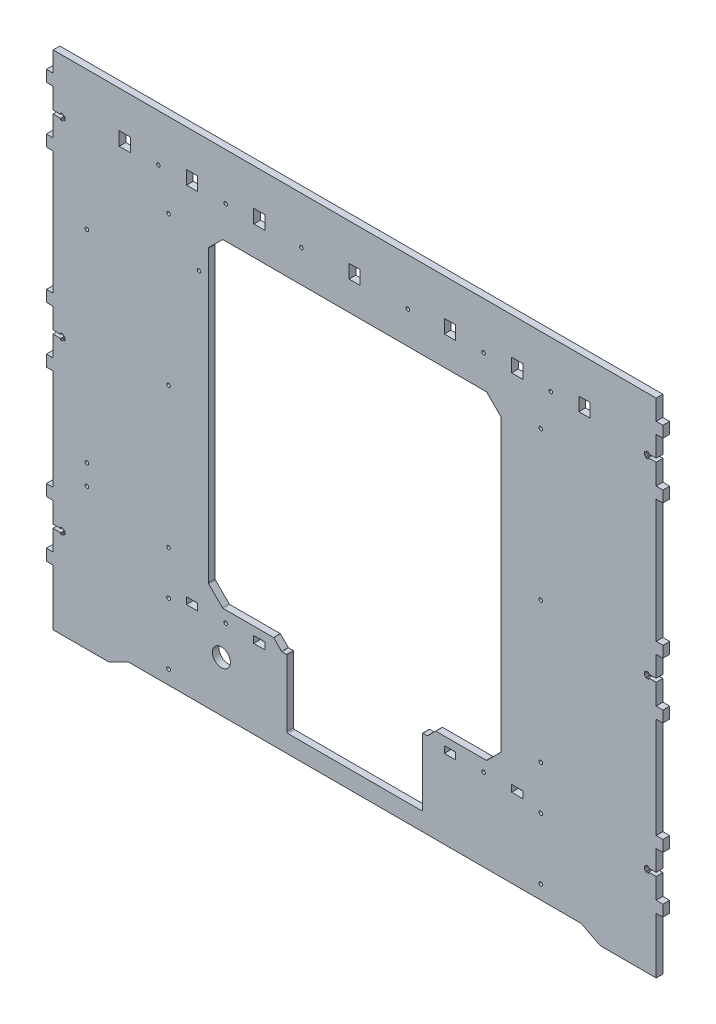
SolidWorks part; units mm, degrees
material "Клен"
ref_plane "Front" through (0, 0, 0) normal (0, 0, 1) x (1, 0, 0)
ref_plane "Top" through (0, 0, 0) normal (0, 1, 0) x (1, 0, 0)
ref_plane "Right" through (0, 0, 0) normal (1, 0, 0) x (0, 0, -1)
sketch "Эскиз2" plane through (0, 0, 0) normal (0, 0, 1) x (1, 0, 0)
  line L0 (400.4244, 482.0072) -> (-19.6784, 482.0072) construction
  line L1 (308.1919, 504.8221) -> (308.1919, 0) construction
  line L2 (39.1919, 504.8221) -> (39.1919, 18.7975) construction
  line L3 (33.1919, 504.8221) -> (33.1919, 18.7975) construction
  line L4 (228.1919, 149.8356) -> (228.1919, 102.1072) construction
  line L5 (168.1919, 135.3857) -> (168.1919, 108.8729) construction
  line L6 (193.1919, 141.9072) -> (193.1919, 108.8729) construction
  line L7 (260.6919, 457.1072) -> (260.6919, 439.2572) construction
  line L8 (228.1919, 461.9072) -> (228.1919, 439.2572) construction
  line L13 (193.1919, 457.1072) -> (193.1919, 440.4572) construction
  line L18 (39.1919, 477.0072) -> (39.1919, 472.1072)
  line L19 (39.1919, 472.1072) -> (33.1919, 472.0072)
  line L20 (33.1919, 472.0072) -> (33.1919, 462.0072)
  line L21 (33.1919, 462.0072) -> (39.1919, 461.9072)
  line L22 (39.1919, 461.9072) -> (39.1919, 443.5572)
  line L23 (39.1919, 443.5572) -> (45.9919, 443.5572)
  line L24 (45.9919, 443.5572) -> (45.9919, 444.7572)
  line L25 (45.9919, 444.7572) -> (48.1919, 444.7572)
  line L26 (48.1919, 444.7572) -> (48.1919, 443.5572)
  line L27 (48.1919, 443.5572) -> (49.6919, 443.5572)
  line L28 (49.6919, 443.5572) -> (49.6919, 440.4572)
  line L29 (49.6919, 440.4572) -> (48.1919, 440.4572)
  line L30 (48.1919, 440.4572) -> (48.1919, 439.2572)
  line L31 (48.1919, 439.2572) -> (45.9919, 439.2572)
  line L32 (45.9919, 439.2572) -> (45.9919, 440.4572)
  line L33 (45.9919, 440.4572) -> (39.1919, 440.4572)
  line L34 (39.1919, 440.4572) -> (39.1919, 422.1072)
  line L35 (39.1919, 422.1072) -> (33.1919, 422.0072)
  line L36 (33.1919, 422.0072) -> (33.1919, 412.0072)
  line L37 (33.1919, 412.0072) -> (39.1919, 411.9072)
  line L38 (39.1919, 411.9072) -> (39.1919, 302.1072)
  line L39 (39.1919, 302.1072) -> (33.1919, 302.0072)
  line L40 (33.1919, 302.0072) -> (33.1919, 292.0072)
  line L41 (33.1919, 292.0072) -> (39.1919, 291.9072)
  line L42 (39.1919, 291.9072) -> (39.1919, 273.5572)
  line L43 (39.1919, 273.5572) -> (45.9919, 273.5572)
  line L44 (45.9919, 273.5572) -> (45.9919, 274.7572)
  line L45 (45.9919, 274.7572) -> (48.1919, 274.7572)
  line L46 (48.1919, 274.7572) -> (48.1919, 273.5572)
  line L47 (48.1919, 273.5572) -> (49.6919, 273.5572)
  line L48 (49.6919, 273.5572) -> (49.6919, 270.4572)
  line L49 (49.6919, 270.4572) -> (48.1919, 270.4572)
  line L50 (48.1919, 270.4572) -> (48.1919, 269.2572)
  line L51 (48.1919, 269.2572) -> (45.9919, 269.2572)
  line L52 (45.9919, 269.2572) -> (45.9919, 270.4572)
  line L53 (45.9919, 270.4572) -> (39.1919, 270.4572)
  line L54 (39.1919, 270.4572) -> (39.1919, 252.1072)
  line L55 (39.1919, 252.1072) -> (33.1919, 252.0072)
  line L56 (33.1919, 252.0072) -> (33.1919, 242.0072)
  line L57 (33.1919, 242.0072) -> (39.1919, 241.9072)
  line L58 (39.1919, 241.9072) -> (39.1919, 152.1072)
  line L59 (39.1919, 152.1072) -> (33.1919, 152.0072)
  line L60 (33.1919, 152.0072) -> (33.1919, 142.0072)
  line L61 (33.1919, 142.0072) -> (39.1919, 141.9072)
  line L62 (39.1919, 141.9072) -> (39.1919, 123.5572)
  line L63 (39.1919, 123.5572) -> (45.9919, 123.5572)
  line L64 (45.9919, 123.5572) -> (45.9919, 124.7572)
  line L65 (45.9919, 124.7572) -> (48.1919, 124.7572)
  line L66 (48.1919, 124.7572) -> (48.1919, 123.5572)
  line L67 (48.1919, 123.5572) -> (49.6919, 123.5572)
  line L68 (49.6919, 123.5572) -> (49.6919, 120.4572)
  line L69 (49.6919, 120.4572) -> (48.1919, 120.4572)
  line L70 (48.1919, 120.4572) -> (48.1919, 119.2572)
  line L71 (48.1919, 119.2572) -> (45.9919, 119.2572)
  line L72 (45.9919, 119.2572) -> (45.9919, 120.4572)
  line L73 (45.9919, 120.4572) -> (39.1919, 120.4572)
  line L74 (39.1919, 120.4572) -> (39.1919, 102.1072)
  line L75 (39.1919, 102.1072) -> (33.1919, 102.0072)
  line L76 (33.1919, 102.0072) -> (33.1919, 92.0072)
  line L77 (33.1919, 92.0072) -> (39.1919, 91.9072)
  line L78 (39.1919, 91.9072) -> (39.1919, 42.0072)
  line L79 (39.1919, 42.0072) -> (89.1919, 42.0072)
  line L80 (89.1919, 42.0072) -> (106.1919, 50.7072)
  line L81 (106.1919, 50.7072) -> (510.1919, 50.7072)
  line L82 (313.1919, 457.1072) -> (303.1919, 457.1072)
  line L83 (168.1919, 461.9072) -> (168.1919, 439.2572) construction
  line L84 (303.1919, 457.1072) -> (303.1919, 445.0072)
  line L85 (303.1919, 445.0072) -> (313.1919, 445.0072)
  line L86 (267.1919, 490.0072) -> (577.1919, 490.0072)
  line L87 (169.3644, 152.1072) -> (169.3644, 392.271) construction
  line L88 (218.1919, 127.1049) -> (228.1919, 127.1049)
  line L89 (218.1919, 127.1049) -> (218.1919, 121.0049)
  line L90 (218.1919, 121.0049) -> (228.1919, 121.0049)
  line L91 (228.1919, 127.1049) -> (228.1919, 121.0049)
  line L92 (158.1919, 127.1049) -> (168.1919, 127.1049)
  line L93 (158.1919, 127.1049) -> (158.1919, 121.0049)
  line L94 (158.1919, 121.0049) -> (168.1919, 121.0049)
  line L95 (168.1919, 127.1049) -> (168.1919, 121.0049)
  line L96 (158.1919, 457.1072) -> (168.1919, 457.1072)
  line L97 (158.1919, 457.1072) -> (158.1919, 445.0072)
  line L98 (158.1919, 445.0072) -> (168.1919, 445.0072)
  line L99 (168.1919, 457.1072) -> (168.1919, 445.0072)
  line L100 (218.1919, 457.1072) -> (228.1919, 457.1072)
  line L101 (218.1919, 457.1072) -> (218.1919, 445.0072)
  line L102 (218.1919, 445.0072) -> (228.1919, 445.0072)
  line L103 (228.1919, 457.1072) -> (228.1919, 445.0072)
  line L104 (577.1919, 490.0072) -> (577.1919, 477.0072)
  line L105 (367.6919, 66.6049) -> (248.6919, 66.6049)
  line L106 (267.1919, 490.0072) -> (39.1919, 490.0072)
  line L107 (247.6919, 67.6049) -> (247.6919, 126.6049)
  line L108 (247.1919, 127.1049) -> (243.399, 127.1049)
  line L109 (239.5515, 130.7453) -> (243.0455, 127.2514)
  line L110 (39.1919, 490.0072) -> (39.1919, 477.0072)
  line L111 (239.5515, 130.7453) -> (236.0575, 134.2393)
  line L112 (213.3308, 134.3857) -> (235.704, 134.3857)
  line L113 (108.1919, 457.1072) -> (108.1919, 445.0072)
  line L114 (213.3308, 134.3857) -> (190.9576, 134.3857)
  line L115 (184.1064, 140.7795) -> (190.253, 134.6761)
  line L116 (98.1919, 445.0072) -> (108.1919, 445.0072)
  line L117 (184.1064, 140.7795) -> (177.9598, 146.8828)
  line L118 (177.6644, 169.7011) -> (177.6644, 147.5924)
  line L119 (98.1919, 457.1072) -> (108.1919, 457.1072)
  line L120 (177.6644, 169.7011) -> (177.6644, 405.9627)
  line L121 (184.1064, 412.7756) -> (177.9598, 406.6723)
  line L122 (98.1919, 457.1072) -> (98.1919, 445.0072)
  line L123 (184.1064, 412.7756) -> (190.253, 418.8789)
  line L124 (308.1379, 419.1693) -> (190.9576, 419.1693)
  line L125 (518.1919, 457.1072) -> (508.1919, 457.1072)
  line L126 (308.2459, 419.1693) -> (425.4263, 419.1693)
  line L127 (432.2775, 412.7756) -> (426.1309, 418.8789)
  line L128 (432.2775, 412.7756) -> (438.4241, 406.6723)
  line L129 (438.7195, 169.7011) -> (438.7195, 405.9627)
  line L130 (438.7195, 169.7011) -> (438.7195, 147.5924)
  line L131 (432.2775, 140.7795) -> (438.4241, 146.8828)
  line L132 (432.2775, 140.7795) -> (426.1309, 134.6761)
  line L133 (403.0531, 134.3857) -> (425.4263, 134.3857)
  line L134 (403.0531, 134.3857) -> (380.6799, 134.3857)
  line L135 (376.8323, 130.7453) -> (380.3263, 134.2393)
  line L136 (376.8323, 130.7453) -> (373.3384, 127.2514)
  line L137 (369.1919, 127.1049) -> (372.9848, 127.1049)
  line L138 (368.6919, 67.6049) -> (368.6919, 126.6049)
  line L139 (388.1919, 457.1072) -> (388.1919, 445.0072)
  line L140 (398.1919, 445.0072) -> (388.1919, 445.0072)
  line L141 (398.1919, 457.1072) -> (398.1919, 445.0072)
  line L142 (398.1919, 457.1072) -> (388.1919, 457.1072)
  line L143 (448.1919, 457.1072) -> (448.1919, 445.0072)
  line L144 (458.1919, 445.0072) -> (448.1919, 445.0072)
  line L145 (458.1919, 457.1072) -> (458.1919, 445.0072)
  line L146 (458.1919, 457.1072) -> (448.1919, 457.1072)
  line L147 (448.1919, 127.1049) -> (448.1919, 121.0049)
  line L148 (458.1919, 121.0049) -> (448.1919, 121.0049)
  line L149 (458.1919, 127.1049) -> (458.1919, 121.0049)
  line L150 (458.1919, 127.1049) -> (448.1919, 127.1049)
  line L151 (388.1919, 127.1049) -> (388.1919, 121.0049)
  line L152 (398.1919, 121.0049) -> (388.1919, 121.0049)
  line L153 (398.1919, 127.1049) -> (398.1919, 121.0049)
  line L154 (398.1919, 127.1049) -> (388.1919, 127.1049)
  line L155 (313.1919, 457.1072) -> (313.1919, 445.0072)
  line L156 (527.1919, 42.0072) -> (510.1919, 50.7072)
  line L157 (577.1919, 42.0072) -> (527.1919, 42.0072)
  line L158 (577.1919, 91.9072) -> (577.1919, 42.0072)
  line L159 (583.1919, 92.0072) -> (577.1919, 91.9072)
  line L160 (583.1919, 102.0072) -> (583.1919, 92.0072)
  line L161 (577.1919, 102.1072) -> (583.1919, 102.0072)
  line L162 (577.1919, 120.4572) -> (577.1919, 102.1072)
  line L163 (570.3919, 120.4572) -> (577.1919, 120.4572)
  line L164 (570.3919, 119.2572) -> (570.3919, 120.4572)
  line L165 (568.1919, 119.2572) -> (570.3919, 119.2572)
  line L166 (568.1919, 120.4572) -> (568.1919, 119.2572)
  line L167 (566.6919, 120.4572) -> (568.1919, 120.4572)
  line L168 (566.6919, 123.5572) -> (566.6919, 120.4572)
  line L169 (568.1919, 123.5572) -> (566.6919, 123.5572)
  line L170 (568.1919, 124.7572) -> (568.1919, 123.5572)
  line L171 (570.3919, 124.7572) -> (568.1919, 124.7572)
  line L172 (570.3919, 123.5572) -> (570.3919, 124.7572)
  line L173 (577.1919, 123.5572) -> (570.3919, 123.5572)
  line L174 (577.1919, 141.9072) -> (577.1919, 123.5572)
  line L175 (583.1919, 142.0072) -> (577.1919, 141.9072)
  line L176 (583.1919, 152.0072) -> (583.1919, 142.0072)
  line L177 (577.1919, 152.1072) -> (583.1919, 152.0072)
  line L178 (577.1919, 241.9072) -> (577.1919, 152.1072)
  line L179 (583.1919, 242.0072) -> (577.1919, 241.9072)
  line L180 (583.1919, 252.0072) -> (583.1919, 242.0072)
  line L181 (577.1919, 252.1072) -> (583.1919, 252.0072)
  line L182 (577.1919, 270.4572) -> (577.1919, 252.1072)
  line L183 (570.3919, 270.4572) -> (577.1919, 270.4572)
  line L184 (570.3919, 269.2572) -> (570.3919, 270.4572)
  line L185 (568.1919, 269.2572) -> (570.3919, 269.2572)
  line L186 (568.1919, 270.4572) -> (568.1919, 269.2572)
  line L187 (566.6919, 270.4572) -> (568.1919, 270.4572)
  line L188 (566.6919, 273.5572) -> (566.6919, 270.4572)
  line L189 (568.1919, 273.5572) -> (566.6919, 273.5572)
  line L190 (568.1919, 274.7572) -> (568.1919, 273.5572)
  line L191 (570.3919, 274.7572) -> (568.1919, 274.7572)
  line L192 (570.3919, 273.5572) -> (570.3919, 274.7572)
  line L193 (577.1919, 273.5572) -> (570.3919, 273.5572)
  line L194 (577.1919, 291.9072) -> (577.1919, 273.5572)
  line L195 (583.1919, 292.0072) -> (577.1919, 291.9072)
  line L196 (583.1919, 302.0072) -> (583.1919, 292.0072)
  line L197 (577.1919, 302.1072) -> (583.1919, 302.0072)
  line L198 (577.1919, 411.9072) -> (577.1919, 302.1072)
  line L199 (583.1919, 412.0072) -> (577.1919, 411.9072)
  line L200 (583.1919, 422.0072) -> (583.1919, 412.0072)
  line L201 (577.1919, 422.1072) -> (583.1919, 422.0072)
  line L202 (577.1919, 440.4572) -> (577.1919, 422.1072)
  line L203 (570.3919, 440.4572) -> (577.1919, 440.4572)
  line L204 (570.3919, 439.2572) -> (570.3919, 440.4572)
  line L205 (568.1919, 439.2572) -> (570.3919, 439.2572)
  line L206 (568.1919, 440.4572) -> (568.1919, 439.2572)
  line L207 (566.6919, 440.4572) -> (568.1919, 440.4572)
  line L208 (566.6919, 443.5572) -> (566.6919, 440.4572)
  line L209 (568.1919, 443.5572) -> (566.6919, 443.5572)
  line L210 (568.1919, 444.7572) -> (568.1919, 443.5572)
  line L211 (570.3919, 444.7572) -> (568.1919, 444.7572)
  line L212 (570.3919, 443.5572) -> (570.3919, 444.7572)
  line L213 (577.1919, 443.5572) -> (570.3919, 443.5572)
  line L214 (577.1919, 461.9072) -> (577.1919, 443.5572)
  line L215 (583.1919, 462.0072) -> (577.1919, 461.9072)
  line L216 (583.1919, 472.0072) -> (583.1919, 462.0072)
  line L217 (577.1919, 472.1072) -> (583.1919, 472.0072)
  line L218 (577.1919, 477.0072) -> (577.1919, 472.1072)
  line L226 (308.1379, 419.1693) -> (308.2459, 419.1693)
  line L227 (508.1919, 457.1072) -> (508.1919, 445.0072)
  line L228 (518.1919, 457.1072) -> (518.1919, 445.0072)
  line L229 (518.1919, 445.0072) -> (508.1919, 445.0072)
  line L230 (474.1919, 504.8221) -> (474.1919, 18.7975) construction
  line L231 (448.1919, 445.0072) -> (600.6121, 445.0072) construction
  line L232 (600.6121, 415.0072) -> (458.1919, 415.0072) construction
  line L233 (600.6121, 157.1049) -> (458.1919, 157.1049) construction
  line L234 (448.1919, 127.1049) -> (600.6121, 127.1049) construction
  line L235 (458.1919, 282.5072) -> (600.6121, 282.5072) construction
  circle A4 centre (260.6919, 448.0572) radius 1.6
  circle A5 centre (193.1919, 448.0572) radius 1.6
  circle A6 centre (169.3644, 384.4593) radius 1.6
  circle A7 centre (69.3644, 366.4593) radius 1.6
  circle A8 centre (69.3644, 186.0893) radius 1.6
  circle A9 centre (69.3644, 168.0893) radius 1.6
  circle A10 centre (193.1919, 124.0549) radius 1.6
  circle A11 centre (142.1919, 117.9049) radius 1.7
  circle A12 centre (142.1919, 63.1049) radius 1.7
  circle A13 centre (189.3045, 95.8269) radius 8.05
  arc A14 (248.6919, 66.6049) -> (247.6919, 67.6049) centre (248.6919, 67.6049) cw
  arc A15 (247.6919, 126.6049) -> (247.1919, 127.1049) centre (247.1919, 126.6049) ccw
  arc A16 (243.0455, 127.2514) -> (243.399, 127.1049) centre (243.399, 127.6049) ccw
  arc A17 (236.0575, 134.2393) -> (235.704, 134.3857) centre (235.704, 133.8857) ccw
  arc A18 (190.9576, 419.1693) -> (190.253, 418.8789) centre (190.9576, 418.1693) ccw
  arc A19 (177.9598, 406.6723) -> (177.6644, 405.9627) centre (178.6644, 405.9627) ccw
  arc A20 (177.9598, 146.8828) -> (177.6644, 147.5924) centre (178.6644, 147.5924) cw
  arc A21 (190.9576, 134.3857) -> (190.253, 134.6761) centre (190.9576, 135.3857) cw
  arc A22 (425.4263, 134.3857) -> (426.1309, 134.6761) centre (425.4263, 135.3857) ccw
  arc A23 (438.4241, 146.8828) -> (438.7195, 147.5924) centre (437.7195, 147.5924) ccw
  arc A24 (438.4241, 406.6723) -> (438.7195, 405.9627) centre (437.7195, 405.9627) cw
  arc A25 (425.4263, 419.1693) -> (426.1309, 418.8789) centre (425.4263, 418.1693) cw
  arc A26 (380.3263, 134.2393) -> (380.6799, 134.3857) centre (380.6799, 133.8857) cw
  arc A27 (373.3384, 127.2514) -> (372.9848, 127.1049) centre (372.9848, 127.6049) cw
  arc A28 (368.6919, 126.6049) -> (369.1919, 127.1049) centre (369.1919, 126.6049) cw
  arc A29 (367.6919, 66.6049) -> (368.6919, 67.6049) centre (367.6919, 67.6049) ccw
  circle A30 centre (474.1919, 63.1049) radius 1.7
  circle A31 centre (474.1919, 117.9049) radius 1.7
  circle A32 centre (423.1919, 124.0549) radius 1.6
  circle A33 centre (423.1919, 448.0572) radius 1.6
  circle A34 centre (355.6919, 448.0572) radius 1.6
  circle A35 centre (483.1919, 448.0572) radius 1.6
  circle A36 centre (133.1919, 448.0572) radius 1.6
  circle A37 centre (474.1919, 415.0072) radius 1.6
  circle A38 centre (474.1919, 282.5072) radius 1.6
  circle A39 centre (474.1919, 157.1049) radius 1.6
  circle A40 centre (142.1919, 157.1049) radius 1.6
  circle A41 centre (142.1919, 282.5072) radius 1.6
  circle A42 centre (142.1919, 415.0072) radius 1.6
  point P40 (577.1919, 357.0072)
  point P331 (308.1919, 66.6049)
  point P348 (308.1919, 445.0072)
  point P349 (308.1919, 457.1072)
  dimension "D3" = 103
  dimension "D4" = 30
  dimension "D5" = 1
  dimension "D6" = 0.5
  dimension "D7" = 0.5
  dimension "D8" = 0.5
  dimension "D9" = 1
  dimension "D10" = 1
  dimension "D11" = 1
  dimension "D12" = 1
  dimension "D15" = 58.3874
  dimension "D26" = 3.2
  dimension "D27" = 3.2
  dimension "D28" = 3.2
  dimension "D13" = 6
  dimension "D14" = 269
  dimension "D16" = 47.5
  dimension "D17" = 32.5
  dimension "D18" = 35
  dimension "D19" = 25
  dimension "D20" = 30
  dimension "D21" = 138.8276
  dimension "D22" = 80
  dimension "D23" = 35
  dimension "D24" = 25
  dimension "D25" = 162.5
extrude "Бобышка-Вытянуть2" add sketch "Эскиз2" along normal blind 6
